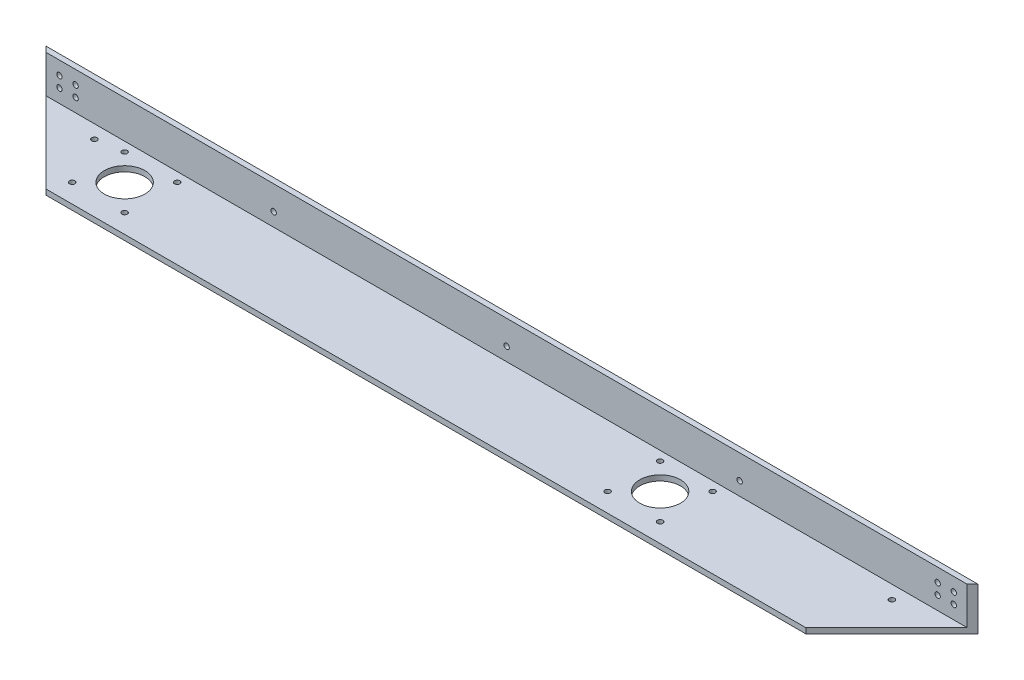
SolidWorks part; units mm, degrees
ref_plane "Front Plane" through (0, 0, 0) normal (0, 0, 1) x (1, 0, 0)
ref_plane "Top Plane" through (0, 0, 0) normal (0, 1, 0) x (1, 0, 0)
ref_plane "Right Plane" through (0, 0, 0) normal (1, 0, 0) x (0, 0, -1)
sketch "Sketch1" plane through (0, 0, 0) normal (1, 0, 0) x (0, 0, -1)
  line L0 (0, 0) -> (-50.8, 0)
  line L1 (-50.8, 0) -> (-50.8, 3.175)
  line L2 (-50.8, 3.175) -> (-3.175, 3.175)
  line L3 (-3.175, 3.175) -> (-3.175, 25.4)
  line L4 (-3.175, 25.4) -> (0, 25.4)
  line L5 (0, 25.4) -> (0, 0)
  dimension "LHeight" = 25.4
  dimension "LWidth" = 50.8
  dimension "LMaterialThickness" = 3.175
  dimension "D1" = 47.625
  dimension "D2" = 22.225
  dimension "D3" = 3.175
extrude "Boss-Extrude1" add sketch "Sketch1" along normal blind 550
chamfer "Chamfer7" distance 50.8 angle 45 1 edges at (0, 1.5875, 50.8)
chamfer "Chamfer8" distance 50.8 angle 45 1 edges at (550, 1.5875, 50.8)
sketch "BotthomHoles-Sketch2" plane through (0, 3.175, 0) normal (0, 1, 0) x (1, 0, 0)
  line L0 (546.825, -3.175) -> (3.175, -3.175) construction
  line L1 (550, 0) -> (0, 0) construction
  circle A0 centre (70.575, -24.175) radius 12
  circle A1 centre (386.575, -24.175) radius 12
  circle A2 centre (55.075, -8.675) radius 1.5875
  circle A3 centre (86.075, -8.675) radius 1.5875
  circle A4 centre (371.075, -8.675) radius 1.5875
  circle A5 centre (402.075, -8.675) radius 1.5875
  circle A6 centre (55.075, -39.675) radius 1.5875
  circle A7 centre (86.075, -39.675) radius 1.5875
  circle A8 centre (371.075, -39.675) radius 1.5875
  circle A9 centre (402.075, -39.675) radius 1.5875
  circle A10 centre (39.6875, -11.1125) radius 1.5875
  circle A11 centre (510.3125, -11.1125) radius 1.5875
  dimension "D9" = 3.175
  dimension "D10" = 24
  dimension "D14" = 3.175
  dimension "D2" = 8.675
  dimension "D3" = 31
  dimension "D4" = 15.5
  dimension "D5" = 15.5
  dimension "D6" = 31
  dimension "D7" = 15.5
  dimension "D8" = 31
  dimension "D11" = 21
  dimension "D12" = 316
  dimension "D13" = 70.575
  dimension "D15" = 39.6875
  dimension "D16" = 11.1125
  dimension "D17" = 39.6875
extrude "BottomHoles-Cut-Extrude1" cut sketch "BotthomHoles-Sketch2" against normal through all
sketch "SideHoles-Sketch3" plane through (0, 0, 0) normal (0, 0, -1) x (-1, 0, 0)
  line L1 (-550, 0) -> (-550, 25.4) construction
  circle A0 centre (-538.8875, 17.4625) radius 1.5875
  circle A1 centre (-529.3625, 17.4625) radius 1.5875
  circle A2 centre (-538.8875, 11.1125) radius 1.5875
  circle A3 centre (-529.3625, 11.1125) radius 1.5875
  circle A4 centre (-11.1125, 11.1125) radius 1.5875
  circle A5 centre (-20.6375, 11.1125) radius 1.5875
  circle A6 centre (-20.6375, 17.4625) radius 1.5875
  circle A7 centre (-11.1125, 17.4625) radius 1.5875
  circle A8 centre (-412.5, 11.1125) radius 1.5875
  circle A9 centre (-275, 11.1125) radius 1.5875
  circle A10 centre (-137.5, 11.1125) radius 1.5875
  dimension "D7" = 3.175
  dimension "D1" = 11.1125
  dimension "D2" = 20.6375
  dimension "D3" = 7.9375
  dimension "D4" = 11.1125
  dimension "D5" = 11.1125
  dimension "D6" = 20.6375
  dimension "D8" = 137.5
  dimension "D9" = 137.5
  dimension "D10" = 137.5
extrude "SideHoles-Cut-Extrude2" cut sketch "SideHoles-Sketch3" against normal through all
equation "\"LowerRailWidth\"= 2.00in"
equation "\"LowerRailHeight\"= 1.00in"
equation "\"RailThickness\"= .125in'Spec"
equation "\"SideRailHoleY1FromEdge\"= \"HoleOffsetFromEdge\""
equation "\"SideRailHoleX1FromSide\"= \"HoleOffsetFromSide\""
equation "\"StepperHoleDiameter\"= 24mm"
equation "\"StepperMountingHoleDiameter\"= 3.175mm"
equation "\"SideRailLength\"= 550mm"
equation "\"StepperMountingHoleDistance\"= 31mm'Spec"
equation "\"VSWidth\"= 1.25in'Spec"
equation "\"StepperMountingHoleOffsetFromLeftOrRightSide\"= \"StepperMountingHoleOffsetFromItsSide\" + \"RailThickness\""
equation "\"HoleOffsetFromEdge\"= \"RailThickness\" * 2.5"
equation "\"HoleOffsetFromSide\"= \"RailThickness\" * 3.5"
equation "\"StepperMountingHoleOffsetFromItsSide\"= 5.5mm'Spec"
equation "\"SideRailHoleX2FromSide\"= \"VSWidth\" - \"HoleOffsetFromEdge\" - \"RailThickness\"'Equals 20.6375"
equation "\"FasteningHoleDiameter\"= .125in"
equation "\"SideRailHoleY2FromSide\"= \"HoleOffsetFromSide\""
equation "\"LHeight@Sketch1\"=\"LowerRailHeight\""
equation "\"LWidth@Sketch1\"=\"LowerRailWidth\""
equation "\"D1@Chamfer7\"=\"LowerRailWidth\""
equation "\"D1@Chamfer8\"=\"LowerRailWidth\""
equation "\"D2@BotthomHoles-Sketch2\" = \"StepperMountingHoleOffsetFromLeftOrRightSide\""
equation "\"D3@BotthomHoles-Sketch2\" = \"StepperMountingHoleDistance\""
equation "\"D4@BotthomHoles-Sketch2\" = \"StepperMountingHoleDistance\" / 2"
equation "\"D5@BotthomHoles-Sketch2\"= \"StepperMountingHoleDistance\" / 2"
equation "\"D6@BotthomHoles-Sketch2\" = \"StepperMountingHoleDistance\""
equation "\"D7@BotthomHoles-Sketch2\" = \"StepperMountingHoleDistance\" / 2"
equation "\"D8@BotthomHoles-Sketch2\" = \"StepperMountingHoleDistance\""
equation "\"D9@BotthomHoles-Sketch2\" = \"StepperMountingHoleDiameter\""
equation "\"D10@BotthomHoles-Sketch2\" = \"StepperHoleDiameter\""
equation "\"D1@SideHoles-Sketch3\" = \"SideRailHoleX1FromSide\""
equation "\"D2@SideHoles-Sketch3\" = \"SideRailHoleX2FromSide\""
equation "\"D3@SideHoles-Sketch3\" = \"SideRailHoleY1FromEdge\""
equation "\"D4@SideHoles-Sketch3\" = \"SideRailHoleY2FromSide\""
equation "\"D7@SideHoles-Sketch3\" = \"FasteningHoleDiameter\""
equation "\"D1@Boss-Extrude1\"=\"SideRailLength\""
equation "\"D5@SideHoles-Sketch3\"=\"SideRailHoleX1FromSide\""
equation "\"D6@SideHoles-Sketch3\"=\"SideRailHoleX2FromSide\""
equation "\"DistanceBetweenFrontToBackStepperHoles\"= \"BedLength\" - \"DistanceFromBedFrontToFirstLeftStepperHole\"'Equals 316"
equation "\"BedOverlap\"= 20mm"
equation "\"BedThirdSize\"= 70mm"
equation "\"BedLWidth\"= \"BedThirdSize\" + \"BedOverlap\"'Equals 90"
equation "\"BedInnerSquareWidth\"= \"BedThirdSize\" * 3'Equals 210"
equation "\"BedInnerSquareLength\"= \"BedInnerSquareWidth\""
equation "\"BedLength\"= \"BedInnerSquareLength\" + \"BedLWidth\" * 2 - \"BedOverlap\" * 2 + \"BedIncreasedByLength\"'Equals 350"
equation "\"D12@BotthomHoles-Sketch2\"=\"DistanceBetweenFrontToBackStepperHoles\""
equation "\"DistanceFromFrontSideToFirstLeftStepperHole\"= \"DistanceFromFrontSideToBedFront\" + \"DistanceFromBedFrontToFirstLeftStepperHole\"'Equals 70.575"
equation "\"D13@BotthomHoles-Sketch2\"=\"DistanceFromFrontSideToFirstLeftStepperHole\""
equation "\"DistanceFromBedFrontToFirstLeftStepperHole\"= \"LeadScrewNutPadSize\" + 10mm'Equals 34"
equation "\"DistanceFromFrontSideToBedFront\"= \"RailThickness\" + \"BeltTensionerDepth\" + 10mm'Equals 36.575"
equation "\"BeltTensionerDepth\"= \"BeltTensionerBackWallThickness\" + \"BeltTensionerInnerDepth\"'Equals 23.4"
equation "\"BeltTensionerBackWallThickness\"= 4mm"
equation "\"20TGT2PulleyDiameter\"= 17.9mm'Spec"
equation "\"BeltTensionerSpaceBetweenPulleyAndWall\"= 1.5mm"
equation "\"BeltTensionerInnerDepth\"= \"20TGT2PulleyDiameter\" + \"BeltTensionerSpaceBetweenPulleyAndWall\""
equation "\"BedIncreasedByLength\"= 0mm"
equation "\"LowerCornerBlockWidth\"= \"LowerRailWidth\" - \"RailThickness\" * 2'Room for left front stepper"
equation "\"D14@BotthomHoles-Sketch2\"= \"FasteningHoleDiameter\""
equation "\"D15@BotthomHoles-Sketch2\"=\"LowerCornerBlockX1FromSide\""
equation "\"D16@BotthomHoles-Sketch2\"= \"LowerCornerBlockY1FromSide\""
equation "\"D17@BotthomHoles-Sketch2\"=\"LowerCornerBlockX1FromSide\""
equation "\"LowerCornerBlockY1FromSide\"= \"HoleOffsetFromSide\""
equation "\"LowerCornerBlockX1FromSide\"= \"LowerCornerBlockWidth\" - \"HoleOffsetFromEdge\" + \"RailThickness\""
equation "\"LeadScrewNutMountingHoleFlangeDiameter\"= 22mm'Spec"
equation "\"LeadScrewNutPadSize\"= \"LeadScrewNutMountingHoleFlangeDiameter\" + 2mm'Equals 24"
equation "\"LeftOrRightEnclosureOffsets\"= \"SideRailLength\" / 4"
equation "\"D8@SideHoles-Sketch3\"=\"LeftOrRightEnclosureOffsets\""
equation "\"D9@SideHoles-Sketch3\"=\"LeftOrRightEnclosureOffsets\""
equation "\"D10@SideHoles-Sketch3\"=\"LeftOrRightEnclosureOffsets\""
